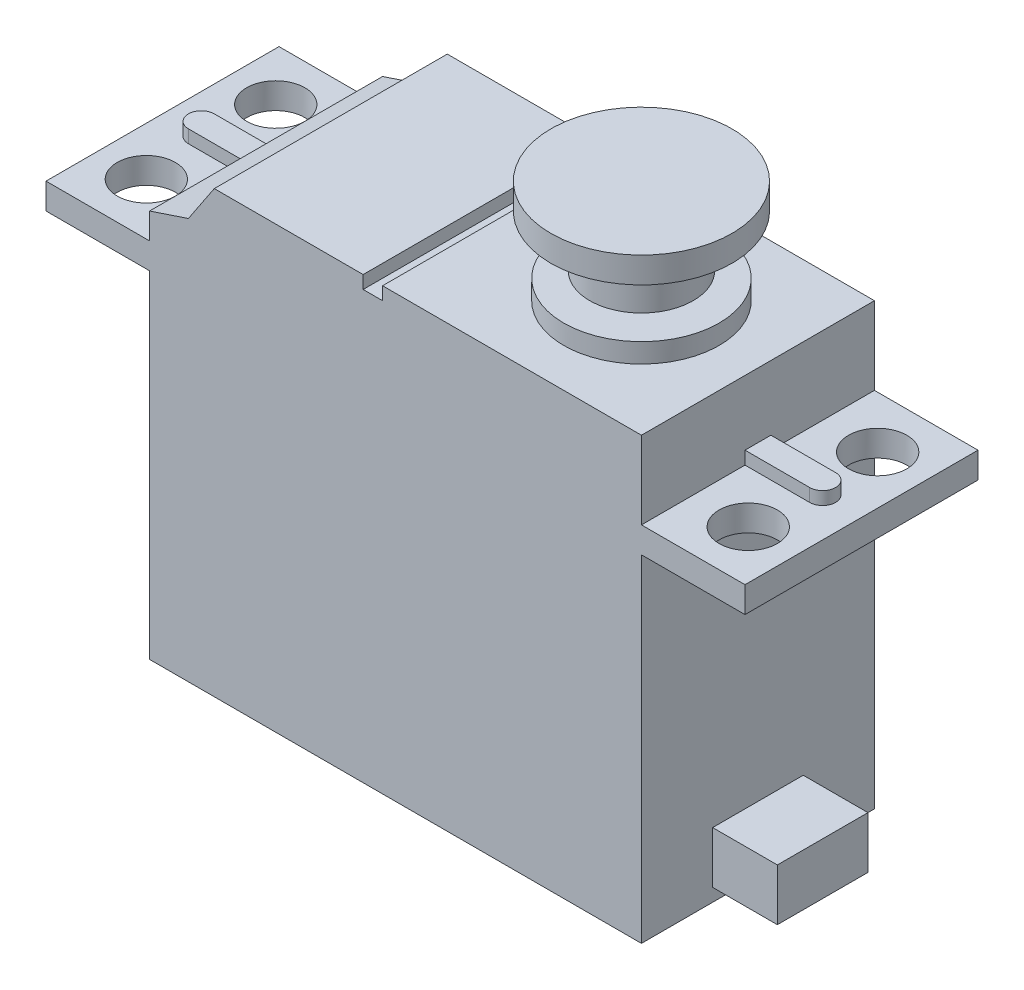
SolidWorks part; units mm, degrees
ref_plane "Front Plane" through (0, 0, 0) normal (0, 0, 1) x (1, 0, 0)
ref_plane "Top Plane" through (0, 0, 0) normal (0, 1, 0) x (1, 0, 0)
ref_plane "Right Plane" through (0, 0, 0) normal (1, 0, 0) x (0, 0, -1)
sketch "Sketch1" plane through (0, 0, 0) normal (0, 1, 0) x (1, 0, 0)
  line L1 (-19, -9) -> (19, -9)
  line L2 (-19, -9) -> (-19, 9)
  line L3 (-19, 9) -> (19, 9)
  line L4 (19, -9) -> (19, 9)
  line L5 (-19, -9) -> (19, 9) construction
  line L6 (-19, 9) -> (19, -9) construction
  point P0 (0, 0)
  dimension "D1" = 18
  dimension "D2" = 38
extrude "Boss-Extrude1" add sketch "Sketch1" along normal blind 34
sketch "Sketch2" plane through (0, 34, 0) normal (0, 1, 0) x (1, 0, 0)
  line L1 (-27, -9) -> (27, -9)
  line L2 (-27, -9) -> (-27, 9)
  line L3 (-27, 9) -> (27, 9)
  line L4 (27, -9) -> (27, 9)
  line L5 (-27, -9) -> (27, 9) construction
  line L6 (-27, 9) -> (27, -9) construction
  line L7 (19, 9) -> (-19, 9) construction
  line L8 (-19, 9) -> (-19, -9) construction
  point P0 (0, 0)
  dimension "D1" = 8
extrude "Boss-Extrude2" add sketch "Sketch2" against normal blind 2 from offset 6 offset against normal yes
sketch "Sketch3" plane through (0, 0, 9) normal (0, 0, 1) x (1, 0, 0)
  line L0 (-19, 30) -> (-16, 31)
  line L1 (-19, 34) -> (-19, 28) construction
  line L2 (-16, 31) -> (-14, 34)
  line L3 (-19, 34) -> (19, 34) construction
  line L4 (-14, 34) -> (-19, 34)
  line L5 (-19, 34) -> (-19, 30)
  line L6 (-27, 28) -> (-19, 28) construction
  line L7 (19, 34) -> (19, 28) construction
  line L8 (-2.5, 34) -> (-1, 34)
  line L9 (-2.5, 34) -> (-2.5, 33)
  line L10 (-2.5, 33) -> (-1, 33)
  line L11 (-1, 34) -> (-1, 33)
  dimension "D1" = 5
  dimension "D2" = 3
  dimension "D3" = 2
  dimension "D4" = 1
  dimension "D5" = 1.5
  dimension "D6" = 1
  dimension "D7" = 20
extrude "Cut-Extrude1" cut sketch "Sketch3" against normal through all both and the other way through all
sketch "Sketch4" plane through (0, 34, 0) normal (0, 1, 0) x (1, 0, 0)
  line L0 (19, -9) -> (19, 9) construction
  circle A0 centre (10, 0) radius 6
  point P5 (16, 0)
  dimension "D1" = 12
  dimension "D2" = 3
extrude "Boss-Extrude3" add sketch "Sketch4" along normal blind 1.5
sketch "Sketch5" plane through (0, 28, 0) normal (0, 1, 0) x (1, 0, 0)
  line L0 (-19, -9) -> (-19, 9) construction
  line L1 (-25, -1) -> (-19, -1)
  line L2 (-25, -1) -> (-25, 1)
  line L3 (-25, 1) -> (-19, 1)
  line L4 (-19, -1) -> (-19, 1)
  line L5 (-25, -1) -> (-19, 1) construction
  line L6 (-25, 1) -> (-19, -1) construction
  point P0 (-22, 0)
  dimension "D1" = 6
  dimension "D2" = 2
extrude "Boss-Extrude4" add sketch "Sketch5" along normal blind 1
fillet "Fillet1" 2 edges at (-25, 28.5, -1) (-25, 28.5, 1) type full round first side face at (-22, 28.5, -1) second side face at (-22, 28.5, 1) middle face at (-25, 28.5, 0)
mirror "Mirror1" about plane through (0, 0, 0) normal (1, 0, 0) of "Boss-Extrude4", "Fillet1"
sketch "Sketch6" plane through (19, 0, 0) normal (1, 0, 0) x (0, 0, -1)
  line L0 (-9, 0) -> (9, 0) construction
  line L1 (-3.5, 1) -> (3.5, 1)
  line L2 (-3.5, 1) -> (-3.5, 5)
  line L3 (-3.5, 5) -> (3.5, 5)
  line L4 (3.5, 1) -> (3.5, 5)
  line L5 (-3.5, 1) -> (3.5, 5) construction
  line L6 (-3.5, 5) -> (3.5, 1) construction
  point P0 (0, 3)
  dimension "D1" = 4
  dimension "D2" = 7
  dimension "D3" = 1
extrude "Boss-Extrude5" add sketch "Sketch6" along normal blind 5
sketch "Sketch7" plane through (0, 35.5, 0) normal (0, 1, 0) x (1, 0, 0)
  circle A0 centre (10, 0) radius 3
  circle A1 centre (10, 0) radius 6 construction
  dimension "D1" = 6
extrude "Boss-Extrude6" add sketch "Sketch7" along normal blind 4
sketch "Sketch8" plane through (0, 34, 0) normal (0, 1, 0) x (1, 0, 0)
  circle A0 centre (10, 0) radius 7
  dimension "D1" = 14
extrude "Boss-Extrude7" add sketch "Sketch8" against normal blind 2 from offset 8 separate body
sketch "Sketch9" plane through (0, 40, 0) normal (0, -1, 0) x (1, 0, 0)
  circle A0 centre (10, 0) radius 4
  dimension "D1" = 8
extrude "Boss-Extrude8" add sketch "Sketch9" along normal blind 4
sketch "Sketch10" plane through (0, 28, 0) normal (0, 1, 0) x (1, 0, 0)
  line L0 (-19, 1) -> (-19, 9) construction
  line L1 (-19, 9) -> (-27, 9) construction
  line L2 (-23.25, 9) -> (-23.25, 1) construction
  line L3 (-19, 1) -> (-24, 1) construction
  circle A0 centre (-23.25, 5) radius 2.25
  point P2 (-23.25, 5)
  point P3 (-21, 5)
  point P11 (-21, 5)
  dimension "D1" = 4.5
  dimension "D2" = 2
extrude "Cut-Extrude2" cut sketch "Sketch10" against normal blind 4
mirror "Mirror2" about plane through (0, 0, 0) normal (0, 0, 1) of "Cut-Extrude2" second plane through (0, 0, 0) second plane normal (1, 0, 0)
sketch "Sketch11" plane through (0, 34, 0) normal (0, 1, 0) x (1, 0, 0)
  line L0 (10, 0) -> (27, 0)
  line L2 (-27, 9) -> (27, 9)
  line L3 (-27, 9) -> (-27, -9)
  line L4 (-27, -9) -> (27, -9)
  line L5 (27, 9) -> (27, -9)
sketch "Sketch12" plane through (0, 34, 0) normal (0, 1, 0) x (1, 0, 0)
  line L0 (-23.25, -5) -> (-23.25, 5)
  line L1 (-23.25, 5) -> (23.25, 5)
